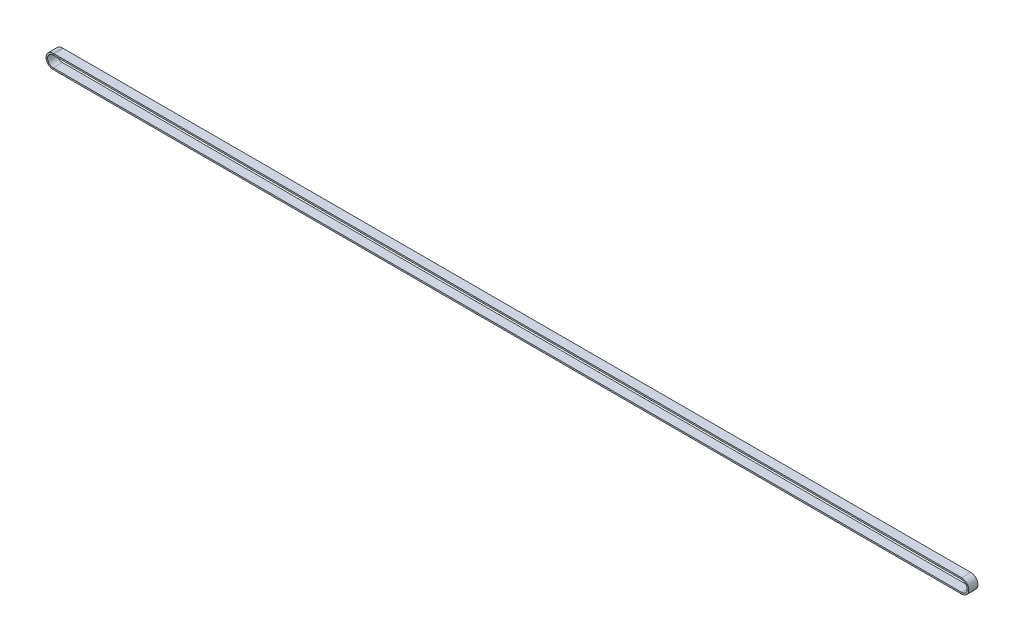
SolidWorks part; units mm, degrees
ref_plane "Front Plane" through (0, 0, 0) normal (0, 0, 1) x (1, 0, 0)
ref_plane "Top Plane" through (0, 0, 0) normal (0, 1, 0) x (1, 0, 0)
ref_plane "Right Plane" through (0, 0, 0) normal (1, 0, 0) x (0, 0, -1)
sketch "Sketch2" plane through (0, 0, -19.2334) normal (0, 0, 1) x (1, 0, 0)
  line L0 (0, 0) -> (1, 0) construction
  line L1 (0, 0) -> (0, 1) construction
  line L2 (-1, -57.6945) -> (883.5206, -57.6945)
  line L3 (883.5206, -71.4945) -> (-1, -71.4945)
  arc A0 (-1, -71.4945) -> (-1, -57.6945) centre (-1, -64.5945) cw
  arc A1 (883.5206, -57.6945) -> (883.5206, -71.4945) centre (883.5206, -64.5945) cw
sketch "Sketch3" plane through (0, 0, 0) normal (1, 0, 0) x (0, 0, -1)
  line L1 (19.2334, -59.1945) -> (10.2334, -59.1945)
  line L2 (19.2334, -59.1945) -> (19.2334, -57.6945)
  line L3 (19.2334, -57.6945) -> (10.2334, -57.6945)
  line L4 (10.2334, -59.1945) -> (10.2334, -57.6945)
  dimension "D1" = 9
  dimension "D2" = 1.5
sweep "Sweep1" add profiles "Sketch3" path "Sketch2"
